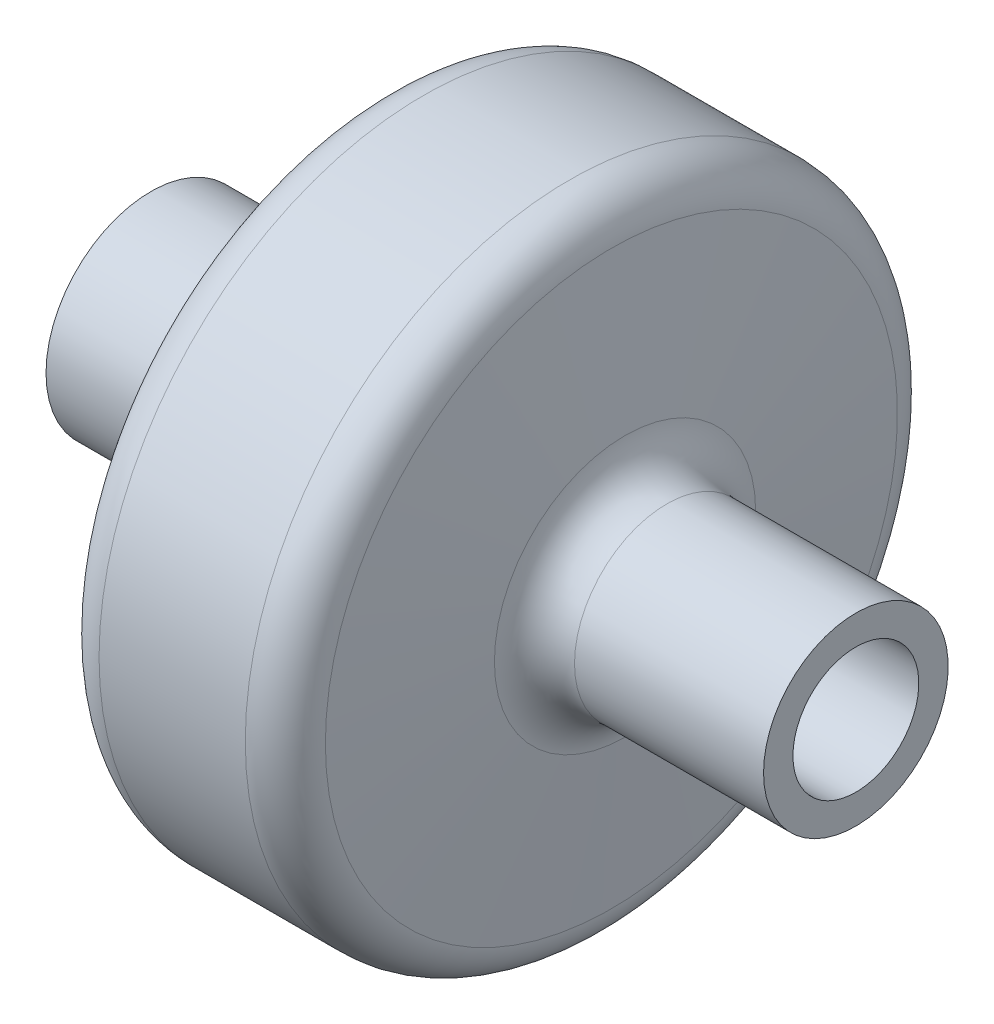
SolidWorks part; units mm, degrees
ref_plane "Front" through (0, 0, 0) normal (0, 0, 1) x (1, 0, 0)
ref_plane "Top" through (0, 0, 0) normal (0, 1, 0) x (1, 0, 0)
ref_plane "Right" through (0, 0, 0) normal (1, 0, 0) x (0, 0, -1)
ref_axis "Axis1" through (0, 0, 55) along (0, 0, -1)
sketch "Sketch1" plane through (0, 0, 0) normal (0, 0, 1) x (1, 0, 0)
  line L0 (-39.9221, 0) -> (39.9221, 0) construction
  line L3 (-6.5329, 36.65) -> (6.5329, 36.65)
  line L4 (11.5329, 31.65) -> (11.5329, 7.5)
  line L5 (11.5329, 7.5) -> (43.0582, 7.5)
  line L6 (43.0582, 7.5) -> (43.0582, 11)
  line L7 (43.0582, 11) -> (20.5336, 11)
  line L8 (13.5329, 11) -> (13.5329, 38.65) construction
  line L9 (8.9512, 38.65) -> (-8.4718, 38.65)
  line L10 (-13.0535, 38.65) -> (-13.0535, 11) construction
  line L12 (-40.9418, 12.5) -> (-40.9418, 11)
  line L13 (0, 0) -> (0, 36.65) construction
  line L14 (-13.4528, 34.0858) -> (-15.0732, 15.5642)
  line L15 (13.9322, 34.0858) -> (15.5526, 15.5642)
  line L16 (-11.5329, 11) -> (15.9519, 11) construction
  line L17 (-18.4172, 12.5) -> (-40.9418, 12.5)
  line L18 (-40.9418, 11) -> (-20.9903, 11)
  line L19 (-11.5329, 31.65) -> (-11.5329, 11)
  line L20 (-11.5329, 11) -> (-20.9903, 11)
  arc A0 (-6.5329, 36.65) -> (-11.5329, 31.65) centre (-6.5329, 31.65) ccw
  arc A1 (11.5329, 31.65) -> (6.5329, 36.65) centre (6.5329, 31.65) ccw
  arc A2 (13.9322, 34.0858) -> (8.9512, 38.65) centre (8.9512, 33.65) ccw
  arc A3 (-13.4528, 34.0858) -> (-8.4718, 38.65) centre (-8.4718, 33.65) cw
  arc A4 (20.5336, 11) -> (15.5526, 15.5642) centre (20.5336, 16) cw
  arc A5 (-18.4172, 12.5) -> (-15.0732, 15.5642) centre (-18.4172, 15.8568) ccw
  point P4 (0, 0)
  point P19 (13.5329, 24.825)
  dimension "D10" = 5
  dimension "D11" = 5
  dimension "D14" = 3.3568
  dimension "D2" = 22
  dimension "D3" = 15
  dimension "D4" = 22
  dimension "D5" = 2
  dimension "D6" = 2
  dimension "D7" = 77.3
  dimension "D8" = 25.0658
  dimension "D9" = 27.385
  dimension "D12" = 4.0197
  dimension "D13" = 25
  dimension "D15" = 84
revolve "Revolve1" add sketch "Sketch1" angle 360 about L0
